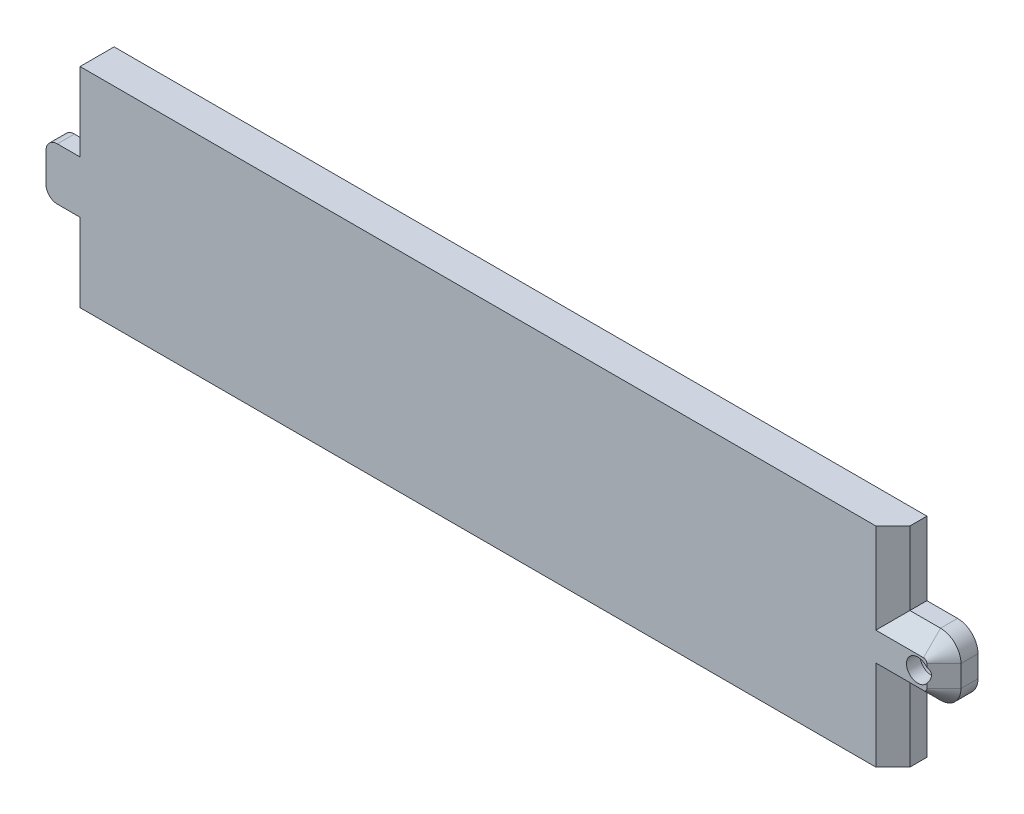
SolidWorks part; units mm, degrees
ref_plane "前视基准面" through (0, 0, 0) normal (0, 0, 1) x (1, 0, 0)
ref_plane "上视基准面" through (0, 0, 0) normal (0, 1, 0) x (1, 0, 0)
ref_plane "右视基准面" through (0, 0, 0) normal (1, 0, 0) x (0, 0, -1)
sketch "草图1" plane through (0, 0, 0) normal (0, 0, 1) x (1, 0, 0)
  line L1 (-35.8, 9.2) -> (35.8, 9.2)
  line L2 (-35.8, 9.2) -> (-35.8, -9.2)
  line L3 (-35.8, -9.2) -> (35.8, -9.2)
  line L4 (35.8, 9.2) -> (35.8, -9.2)
  line L5 (-35.8, 9.2) -> (35.8, -9.2) construction
  line L6 (-35.8, -9.2) -> (35.8, 9.2) construction
  point P0 (0, 0)
  dimension "D1" = 18.4
  dimension "D2" = 71.6
extrude "凸台-拉伸1" add sketch "草图1" along normal blind 3
sketch "草图3" plane through (0, 0, 0) normal (0, 0, -1) x (-1, 0, 0)
  line L0 (-35.8, -9.2) -> (-35.8, 9.2) construction
  line L1 (-31.3, 2.75) -> (-38.5, 2.75)
  line L2 (-31.3, 2.75) -> (-31.3, -2.75)
  line L3 (-31.3, -2.75) -> (-38.5, -2.75)
  line L4 (-40.3, 0.95) -> (-40.3, -0.95)
  line L5 (-31.3, 2.75) -> (-40.3, -2.75) construction
  line L6 (-31.3, -2.75) -> (-40.3, 2.75) construction
  arc A0 (-38.5, -2.75) -> (-40.3, -0.95) centre (-38.5, -0.95) cw
  arc A1 (-38.5, 2.75) -> (-40.3, 0.95) centre (-38.5, 0.95) ccw
  circle A2 centre (-38, 0.05) radius 1
  point P0 (-35.8, 0)
  dimension "D3" = 1.8
  dimension "D4" = 2
  dimension "D1" = 5.5
  dimension "D2" = 9
extrude "凸台-拉伸2" add sketch "草图3" against normal blind 3
sketch "草图4" plane through (0, 0, 0) normal (0, 0, -1) x (-1, 0, 0)
  circle A0 centre (-38, 0.05) radius 1.85
  dimension "D1" = 3.7
extrude "切除-拉伸1" cut sketch "草图4" against normal blind 1.8
sketch "草图5" plane through (0, 0, 0) normal (0, 0, -1) x (-1, 0, 0)
  line L0 (35.8, 9.2) -> (35.8, -9.2) construction
  line L1 (32.8, 2.3) -> (37.8, 2.3)
  line L2 (32.8, 2.3) -> (32.8, -2.3)
  line L3 (32.8, -2.3) -> (37.8, -2.3)
  line L4 (38.8, 1.3) -> (38.8, -1.3)
  line L5 (32.8, 2.3) -> (38.8, -2.3) construction
  line L6 (32.8, -2.3) -> (38.8, 2.3) construction
  arc A0 (37.8, -2.3) -> (38.8, -1.3) centre (37.8, -1.3) ccw
  arc A1 (37.8, 2.3) -> (38.8, 1.3) centre (37.8, 1.3) cw
  point P0 (35.8, 0)
  line M16 (35.8, -9.2) -> (35.8, 9.2)
  dimension "D3" = 1
  dimension "D1" = 4.6
  dimension "D2" = 6
extrude "凸台-拉伸3" add sketch "草图5" against normal blind 1.5 from offset 1.5 contours A1 L1 L3 A0 L4 M16 region at (-37.259, 0, 0) offset against normal yes
chamfer "倒角1" distance 1.5 angle 45 7 edges at (37.15, 2.75, 3) (39.7728, 2.2228, 3) (40.3, 0, 3) (37.15, -2.75, 3) (39.7728, -2.2228, 3) (35.8, 5.975, 3) (35.8, -5.975, 3)
